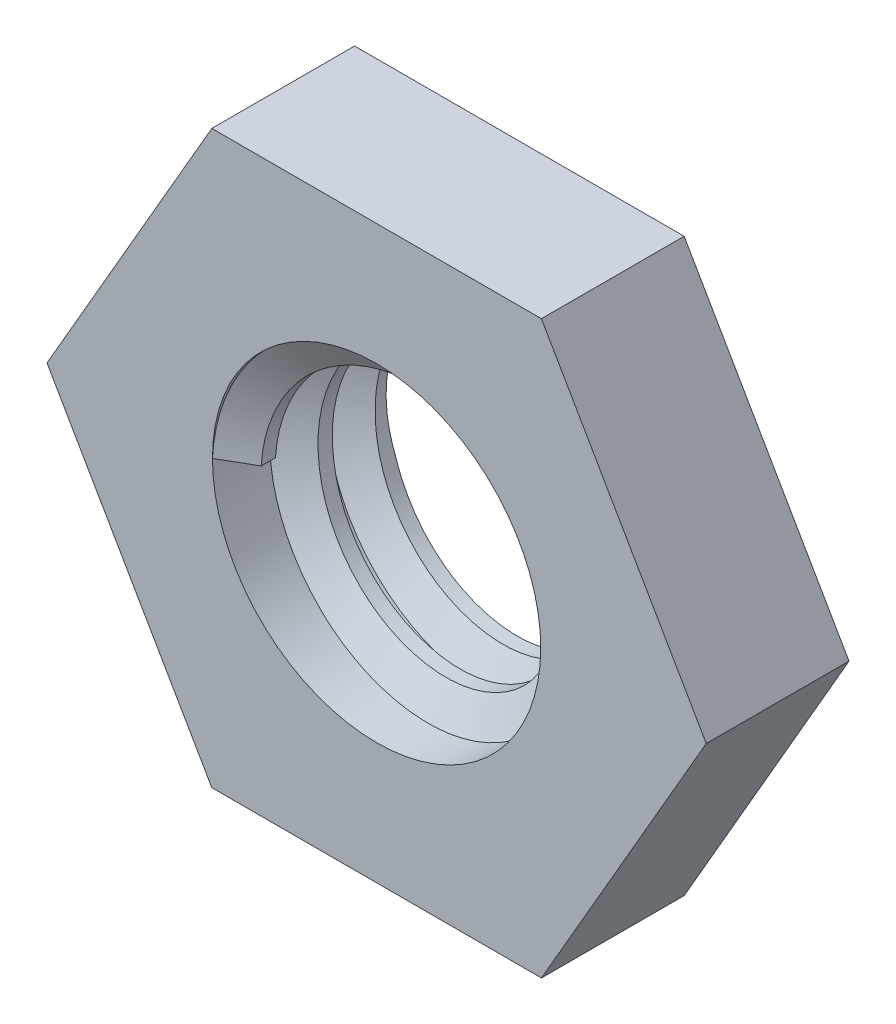
SolidWorks part; units mm, degrees
ref_plane "Ebene vorne" through (0, 0, 0) normal (0, 0, 1) x (1, 0, 0)
ref_plane "Ebene oben" through (0, 0, 0) normal (0, 1, 0) x (1, 0, 0)
ref_plane "Ebene rechts" through (0, 0, 0) normal (1, 0, 0) x (0, 0, -1)
sketch "Skizze1" plane through (0, 0, 0) normal (0, 0, 1) x (1, 0, 0)
  line L0 (0, 0) -> (11.545, 0)
  line L1 (11.545, 0) -> (17.3195, -10.0017)
  line L2 (17.3195, -10.0017) -> (11.547, -20)
  line L3 (11.547, -20) -> (-0.002, -20)
  line L4 (-0.002, -20) -> (-5.7745, -10.0017)
  line L5 (-5.7745, -10.0017) -> (0, 0)
  dimension "D1" = 20
  dimension "D2" = 20
  dimension "D3" = 20
  dimension "D4" = 120
  dimension "D5" = 120
  dimension "D6" = 120
  dimension "D7" = 120
  dimension "D8" = 120
  dimension "D9" = 120
  dimension "D10" = 23.094
  dimension "D11" = 11.545
  dimension "D12" = 11.549
  dimension "D13" = 11.549
extrude "Aufsatz-Linear austragen1" add sketch "Skizze1" along normal blind 5
hole_wizard "Gewindebohrung für Pg7 Führung1" positions "3D-Skizze1" profile "Skizze6" tap size "Pg7" standard "DIN" end condition through all
sketch3d "3D-Skizze1"
  line L0 (11.545, 0, 5) -> (0, 0, 5) construction
  line L1 (-0.002, -20, 5) -> (11.547, -20, 5) construction
  line L2 (17.3195, -10.0017, 5) -> (11.545, 0, 5) construction
  line L3 (11.547, -20, 5) -> (17.3195, -10.0017, 5) construction
  point P5 (5.7715, -10, 5)
  dimension "D1" = 10
  dimension "D2" = 10
  dimension "D3" = 10
  dimension "D4" = 10.0017
sketch "Skizze6" plane through (5.7715, -10, 5) normal (1, 0, 0) x (0, -1, 0)
  line L0 (0, 0) -> (0, 5)
  line L1 (0, 5) -> (5.75, 5)
  line L2 (5.75, 5) -> (5.75, 0)
  line L5 (5.75, 0) -> (0, 0)
  line L11 (0, -6.35) -> (0, 107.95) construction
  dimension "Bohrerdurchmesser" = 11.5
  dimension "Bohrungstiefe" = 5
thread "Gewinde1" pitch 2 method extrude profile "Gewindeprofil2" start angle 0, offset 0, length 10, pitch 2, diameter 11.5
ref_plane "Ebene2" through (0.0215, -10, 5) normal (0, -1, 0) x (-1, 0, 0)
sketch "Gewindeprofil2" plane through (0.0215, -10, 5) normal (0, -1, 0) x (-1, 0, 0)
  line L0 (0, 0) -> (0, 2) construction
  line L11 (0, 0) -> (0, 1.75)
  line L12 (0, 1.75) -> (-1.0825, 1.125)
  line L13 (-1.0825, 1.125) -> (-1.0825, 0.625)
  line L15 (-1.0825, 0.625) -> (0, 0)
  line L17 (-1.0825, 0.875) -> (0, 0.875) construction
  point P2 (0, 0)
  dimension "Pitch" = 2
  dimension "Profile_Angle" = 60
  dimension "Profile_Land" = 0.5
  dimension "Profile_Height" = 1.0825
sketch "Skizze12" plane through (0, 0, 0) normal (0, 0, -1) x (-1, 0, 0)
  line L1 (-13.8504, -1.9685) -> (2.5376, -1.9685)
  line L2 (-13.8504, -1.9685) -> (-13.8504, -18.3255)
  line L3 (-13.8504, -18.3255) -> (2.5376, -18.3255)
  line L4 (2.5376, -1.9685) -> (2.5376, -18.3255)
extrude "Schnitt-Linear austragen1" cut sketch "Skizze12" along normal blind 10
